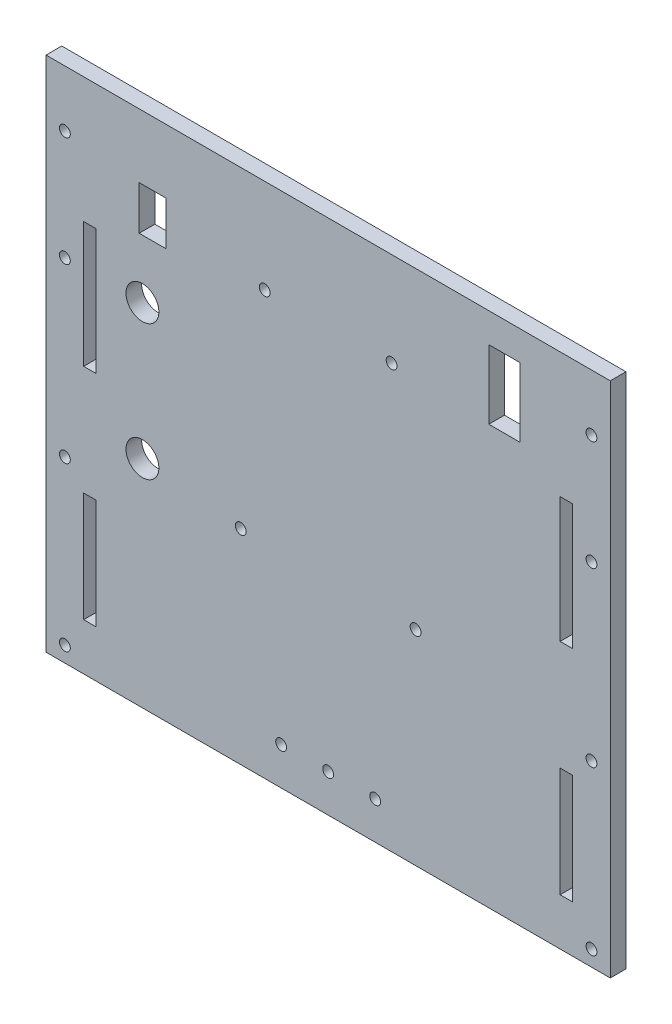
SolidWorks part; units mm, degrees
ref_plane "Front Plane" through (0, 0, 0) normal (0, 0, 1) x (1, 0, 0)
ref_plane "Top Plane" through (0, 0, 0) normal (0, 1, 0) x (1, 0, 0)
ref_plane "Right Plane" through (0, 0, 0) normal (1, 0, 0) x (0, 0, -1)
sketch "Sketch1" plane through (0, 0, 0) normal (0, 0, 1) x (1, 0, 0)
  line L1 (-90, 82.5) -> (90, 82.5)
  line L2 (-90, 82.5) -> (-90, -82.5)
  line L3 (-90, -82.5) -> (90, -82.5)
  line L4 (90, 82.5) -> (90, -82.5)
  line L5 (-90, 82.5) -> (90, -82.5) construction
  line L6 (-90, -82.5) -> (90, 82.5) construction
  point P0 (0, 0)
  dimension "D1" = 165
  dimension "D2" = 180
extrude "Boss-Extrude1" add sketch "Sketch1" along normal blind 5 contours L1 L4 L3 L2
sketch "Sketch2" plane through (0, 0, 5) normal (0, 0, 1) x (1, 0, 0)
  line L3 (-78, 42.5) -> (-78, 2.5)
  line L5 (-78, -82.5) -> (-90, -82.5)
  line L6 (-78, -32.5) -> (-78, -67.5)
  line L7 (-78, 42.5) -> (-74, 42.5)
  line L8 (-74, 42.5) -> (-74, 2.5)
  line L9 (-74, 2.5) -> (-78, 2.5)
  line L11 (-78, -32.5) -> (-74, -32.5)
  line L12 (-74, -32.5) -> (-74, -67.5)
  line L13 (-74, -67.5) -> (-78, -67.5)
  dimension "D4" = 4
  dimension "D5" = 40
  dimension "D6" = 35
  dimension "D7" = 4
  dimension "D8" = 35
extrude "Cut-Extrude1" cut sketch "Sketch2" against normal up to surface (5 mm away) contours L8 L9 L3 L7 up to face at (0, 0, 0)
extrude "Cut-Extrude2" cut sketch "Sketch2<3>" against normal up to surface (5 mm away) contours L12 L13 L6 L11 up to face at (0, 0, 0)
sketch "Sketch2<3>" plane through (0, 0, 5) normal (0, 0, 1) x (1, 0, 0) same geometry as "Sketch2"
mirror "Mirror1" about plane through (0, 0, 0) normal (1, 0, 0) of "Cut-Extrude2", "Cut-Extrude1"
sketch "Sketch3" plane through (0, 0, 0) normal (0, 0, -1) x (-1, 0, 0)
  line L0 (-78, 42.5) -> (-84, 42.5)
  line L1 (-84, 42.5) -> (-84, 82.5)
  line L2 (90, 82.5) -> (-90, 82.5) construction
  line L3 (-84, 82.5) -> (-84, -82.5)
  line L4 (90, -82.5) -> (-90, -82.5) construction
  line L5 (-84, 82.5) -> (-84, 64.5)
  line L6 (-84, 64.5) -> (-84, 29.5)
  line L7 (-84, 29.5) -> (-84, -25.5)
  line L8 (-84, -25.5) -> (-84, -77.5)
  circle A0 centre (-84, -77.5) radius 1.73
  circle A1 centre (-84, -25.5) radius 1.73
  circle A2 centre (-84, 29.5) radius 1.73
  circle A3 centre (-84, 64.5) radius 1.73
  dimension "D6" = 3.46
  dimension "D7" = 3.46
  dimension "D8" = 3.46
  dimension "D9" = 3.46
  dimension "D1" = 6
  dimension "D2" = 18
  dimension "D3" = 35
  dimension "D4" = 55
  dimension "D5" = 52
extrude "Cut-Extrude3" cut sketch "Sketch3" against normal up to surface (5 mm away) contours A0 | A1 | A2 | A3 up to face at (76, -50, 5)
mirror "Mirror2" about plane through (0, 0, 0) normal (1, 0, 0) of "Cut-Extrude3"
sketch "Sketch4" plane through (0, 0, 0) normal (0, 0, -1) x (-1, 0, 0)
  line L0 (0, 82.5) -> (0, -82.5)
  line L1 (90, 82.5) -> (-90, 82.5) construction
  line L2 (90, -82.5) -> (-90, -82.5) construction
  line L3 (-20.24, 52.5) -> (20.24, 52.5)
  line L4 (0, 52.5) -> (0, -17.28)
  line L5 (-20.24, 82.5) -> (-20.24, 52.5)
  line L6 (0, -17.28) -> (27.9, -17.28)
  line L7 (0, -17.28) -> (-27.9, -17.28)
  circle A0 centre (-20.24, 52.5) radius 1.73
  circle A1 centre (20.24, 52.5) radius 1.73
  circle A2 centre (-27.9, -17.28) radius 1.73
  circle A3 centre (27.9, -17.28) radius 1.73
  dimension "D7" = 3.46
  dimension "D8" = 3.46
  dimension "D9" = 3.46
  dimension "D10" = 3.46
  dimension "D1" = 165
  dimension "D2" = 40.48
  dimension "D3" = 69.78
  dimension "D4" = 30
  dimension "D5" = 27.9
  dimension "D6" = 27.9
extrude "Cut-Extrude4" cut sketch "Sketch4" against normal up to surface (5 mm away) contours A0 | A2 | A1 | A3 up to face at (-82.27, -77.5, 5)
sketch "Sketch5" plane through (0, 0, 0) normal (0, 0, -1) x (-1, 0, 0)
  line L0 (-56.2442, 82.5) -> (-56.2442, 73.1174)
  line L1 (90, 82.5) -> (-90, 82.5) construction
  line L2 (90, -82.5) -> (-90, -82.5) construction
  line L3 (-56.2442, 73.1174) -> (-61.2442, 73.1174)
  line L4 (-61.2442, 73.1174) -> (-61.2442, 51.1174)
  line L5 (-61.2442, 51.1174) -> (-51.2442, 51.1174)
  line L6 (-51.2442, 51.1174) -> (-51.2442, 73.1174)
  line L7 (-51.2442, 73.1174) -> (-56.2442, 73.1174)
  line L8 (-56.2442, 51.1174) -> (-56.2442, -82.5)
  line L9 (51.7, 62.1174) -> (60.3, 62.1174)
  line L11 (60.3, 62.1174) -> (56, 62.1174)
  line L12 (56, 62.1174) -> (60.3, 62.1174)
  line L13 (60.3, 62.1174) -> (60.3, 48.1174)
  line L14 (60.3, 48.1174) -> (51.7, 48.1174)
  line L15 (51.7, 48.1174) -> (51.7, 62.1174)
  line L16 (51.7, 62.1174) -> (56, 62.1174)
  line L17 (56, 48.1174) -> (56, -82.5)
  circle A0 centre (59.2604, 29.481) radius 5.25
  circle A1 centre (59.2604, -13.6219) radius 5.25
  dimension "D10" = 10.5
  dimension "D11" = 10.5
  dimension "D1" = 5
  dimension "D2" = 22
  dimension "D3" = 10
  dimension "D4" = 22
  dimension "D6" = 4.3
  dimension "D7" = 14
  dimension "D8" = 8.6
  dimension "D9" = 14
extrude "Cut-Extrude6" cut sketch "Sketch5" against normal up to surface (5 mm away) contours L3 L4 L5 L6 L7 up to face at (-26.17, -17.28, 5)
extrude "Cut-Extrude7" cut sketch "Sketch5<4>" against normal up to surface (5 mm away) contours A1 | A0 | L9 L13 L14 L15 up to face at (56.2442, 62.1174, 5)
sketch "Sketch5<4>" plane through (0, 0, 0) normal (0, 0, -1) x (-1, 0, 0) same geometry as "Sketch5"
sketch "Sketch6" plane through (0, 0, 0) normal (0, 0, -1) x (-1, 0, 0)
  line L0 (0, 82.5) -> (0, -82.5)
  line L1 (90, 82.5) -> (-90, 82.5) construction
  line L2 (90, -82.5) -> (-90, -82.5) construction
  line L3 (0, -82.5) -> (0, -70.5)
  line L4 (0, -70.5) -> (15, -70.5)
  line L5 (15, -70.5) -> (-15, -70.5)
  circle A0 centre (0, -70.5) radius 1.73
  circle A1 centre (-15, -70.5) radius 1.73
  circle A2 centre (15, -70.5) radius 1.73
  dimension "D2" = 3.46
  dimension "D5" = 3.46
  dimension "D6" = 3.46
  dimension "D1" = 12
  dimension "D3" = 15
  dimension "D4" = 30
extrude "Cut-Extrude8" cut sketch "Sketch6" against normal up to surface (5 mm away) contours A1 | A2 | A0 up to face at (-54.0104, -13.6219, 5)
